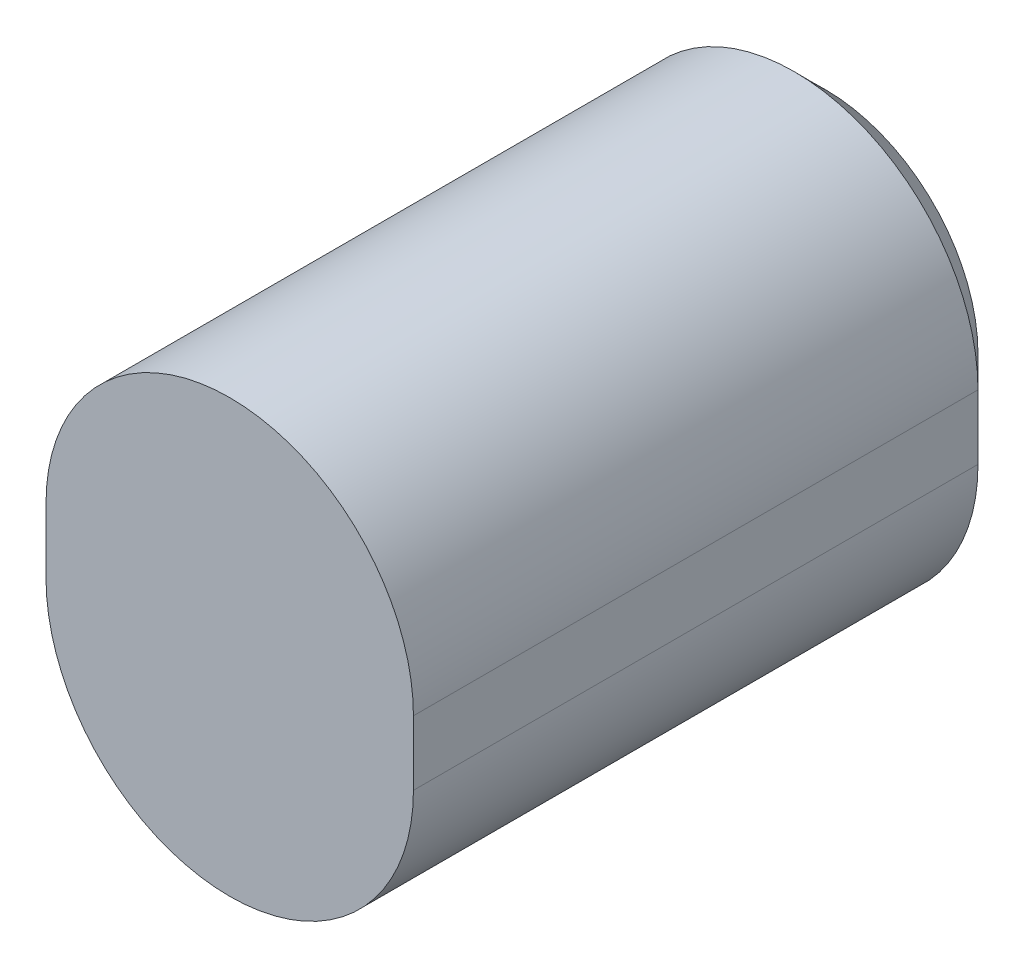
SolidWorks part; units mm, degrees
ref_plane "Front Plane" through (0, 0, 0) normal (0, 0, 1) x (1, 0, 0)
ref_plane "Top Plane" through (0, 0, 0) normal (0, 1, 0) x (1, 0, 0)
ref_plane "Right Plane" through (0, 0, 0) normal (1, 0, 0) x (0, 0, -1)
sketch "Sketch1" plane through (0, 0, 0) normal (0, 0, 1) x (1, 0, 0)
  line L2 (-58.7375, -10.3187) -> (-58.7375, 10.3188)
  line L4 (58.7375, -10.3188) -> (58.7375, 10.3187)
  line L5 (-58.7375, -10.3187) -> (58.7375, 10.3187) construction
  line L6 (-58.7375, 10.3188) -> (58.7375, -10.3188) construction
  arc A0 (-58.7375, 10.3188) -> (58.7375, 10.3187) centre (0, 10.3187) cw
  arc A1 (58.7375, -10.3188) -> (-58.7375, -10.3187) centre (0, -10.3188) cw
  point P0 (0, 0)
  point P9 (0, 69.0562)
  point P10 (0, -69.0563)
  dimension "D1" = 117.475
  dimension "D2" = 138.1125
extrude "Boss-Extrude1" add sketch "Sketch1" along normal blind 190.5
chamfer "Chamfer1" distance 10 angle 45 4 edges at (0, -69.0563, 0) (58.7375, 0, 0) (-58.7375, 0, 0) (0, 69.0563, 0)
